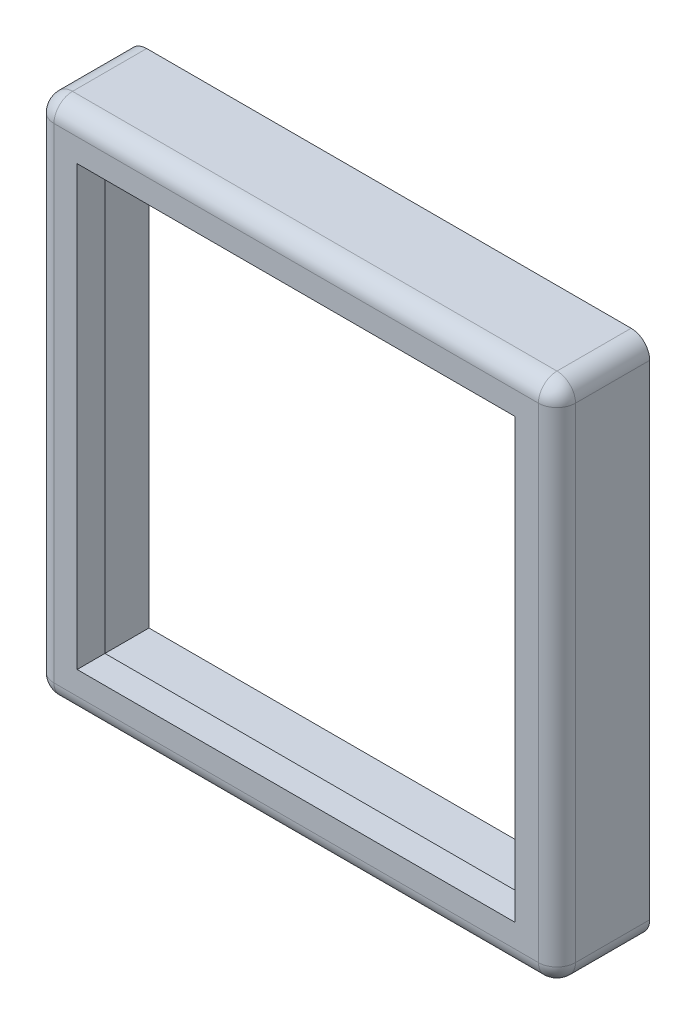
SolidWorks part; units mm, degrees
material "Nylon 101"
ref_plane "Front Plane" through (0, 0, 0) normal (0, 0, 1) x (1, 0, 0)
ref_plane "Top Plane" through (0, 0, 0) normal (0, 1, 0) x (1, 0, 0)
ref_plane "Right Plane" through (0, 0, 0) normal (1, 0, 0) x (0, 0, -1)
sketch "Sketch1" plane through (0, 0, 0) normal (0, 0, 1) x (1, 0, 0)
  line L4 (19.8437, -113.5062) -> (19.8437, -99.2187)
  line L5 (19.8437, -99.2187) -> (5.5562, -99.2187)
  line L6 (5.5562, -99.2187) -> (5.5562, -113.5062)
  line L7 (5.5562, -113.5062) -> (19.8437, -113.5062)
  line L8 (19.8437, -113.5062) -> (19.8437, -99.2187)
  line L9 (19.8437, -99.2187) -> (5.5562, -99.2187)
  line L10 (5.5562, -99.2187) -> (5.5562, -113.5062)
  line L11 (5.5562, -113.5062) -> (19.8437, -113.5062)
  line L13 (18.7007, -100.3617) -> (6.6992, -100.3617)
  line L14 (6.6992, -100.3617) -> (6.6992, -112.3632)
  line L15 (6.6992, -112.3632) -> (18.7007, -112.3632)
  line L16 (18.7007, -112.3632) -> (18.7007, -100.3617)
  line L17 (18.7007, -100.3617) -> (6.6992, -100.3617)
  line L18 (6.6992, -100.3617) -> (6.6992, -112.3632)
  line L19 (6.6992, -112.3632) -> (18.7007, -112.3632)
  line L20 (18.7007, -112.3632) -> (18.7007, -100.3617)
  dimension "D1" = 0
  dimension "D2" = 0
extrude "Boss-Extrude1" add sketch "Sketch1" against normal blind 2.54
sketch "Sketch2" plane through (0, 0, -2.54) normal (0, 0, -1) x (-1, 0, 0)
  line L0 (-6.6992, -112.3632) -> (-5.5562, -113.5062) construction
  line L1 (-18.7007, -100.3617) -> (-19.8437, -99.2187) construction
  line L3 (-19.2722, -99.7902) -> (-6.1277, -99.7902)
  line L4 (-19.2722, -99.7902) -> (-19.2722, -112.9347)
  line L5 (-19.2722, -112.9347) -> (-6.1277, -112.9347)
  line L6 (-6.1277, -99.7902) -> (-6.1277, -112.9347)
  line L7 (-12.7, -112.9347) -> (-12.7, -99.7902) construction
  line L8 (-19.2722, -106.3625) -> (-6.1277, -106.3625) construction
  point P220 (-12.7, -106.3625)
extrude "Cut-Extrude1" cut sketch "Sketch2" against normal offset from surface (1.778 mm away) 0.762 up to face at (12.7, -106.3625, 0)
fillet "Fillet1" radius 0.508 8 edges at (12.7, -113.5062, 0) (5.5562, -106.3625, 0) (12.7, -99.2187, 0) (19.8437, -106.3625, 0) (19.8437, -99.2187, -1.27) (5.5562, -99.2187, -1.27) (5.5562, -113.5062, -1.27) (19.8437, -113.5062, -1.27)
